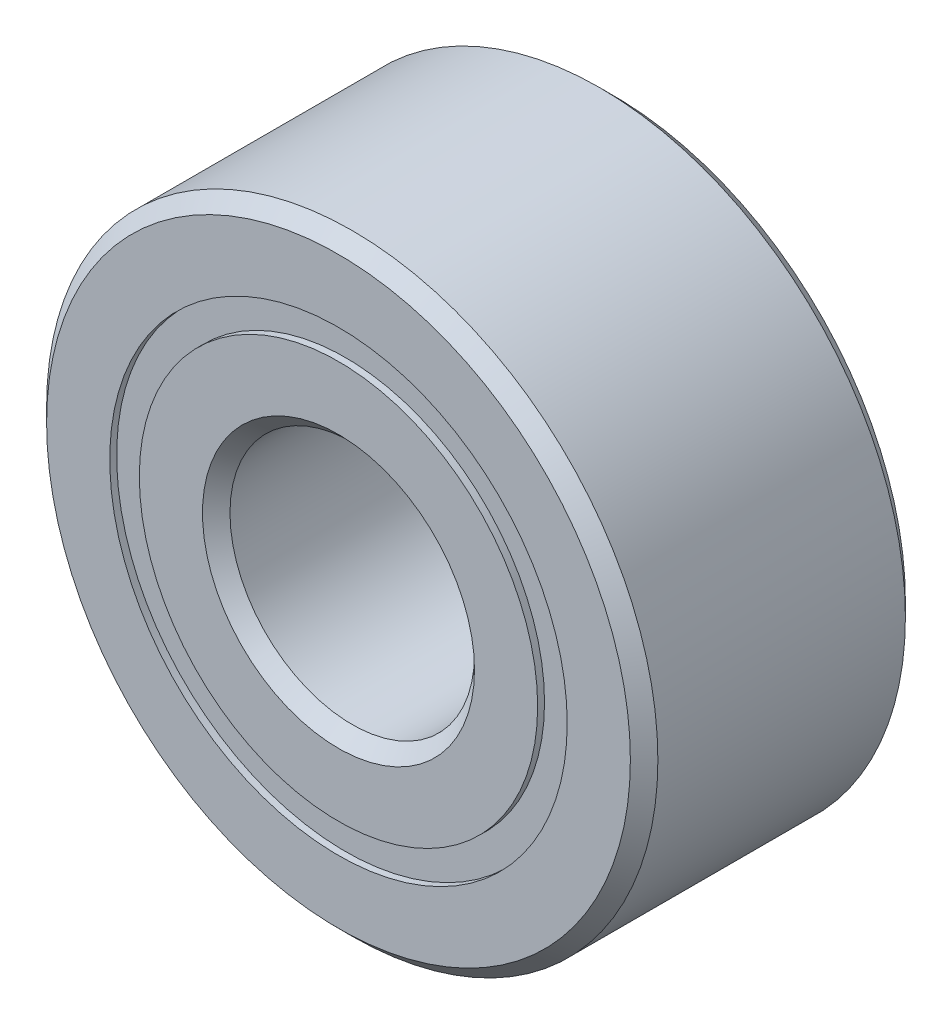
SolidWorks part; units mm, degrees
material "AISI 1020"
ref_plane "Front Plane" through (0, 0, 0) normal (0, 0, 1) x (1, 0, 0)
ref_plane "Top Plane" through (0, 0, 0) normal (0, 1, 0) x (1, 0, 0)
ref_plane "Right Plane" through (0, 0, 0) normal (1, 0, 0) x (0, 0, -1)
sketch "Sketch1" plane through (0, 0, 0) normal (1, 0, 0) x (0, 0, -1)
  line L0 (-1.7856, 0) -> (1.7856, 0) construction
  line L1 (0, 3.9688) -> (0, -3.9688) construction
  line L2 (1.6071, 3.9687) -> (-1.6071, 3.9687)
  line L3 (-1.6071, 3.9687) -> (-1.7856, 3.7902)
  line L4 (-1.7856, 3.7902) -> (-1.7856, 2.97)
  line L5 (-1.7856, 2.97) -> (-0.7936, 2.97)
  line L6 (1.7856, 2.97) -> (0.7936, 2.97)
  line L7 (1.7856, 3.7902) -> (1.7856, 2.97)
  line L8 (1.6071, 3.9687) -> (1.7856, 3.7902)
  line L9 (0, 3.9688) -> (0, 2.7781) construction
  line L10 (0, 2.7781) -> (0, 1.5875) construction
  arc A0 (-0.7936, 2.97) -> (0.7936, 2.97) centre (0, 2.7781) cw
  point P14 (0, 1.5875)
  dimension "D3" = 1.5872
  dimension "D1" = 45
  dimension "Width" = 3.5712
  dimension "OD" = 7.9375
  dimension "D2" = 0.1786
  dimension "Shaft Dia" = 3.175
  dimension "D4" = 0.1919
revolve "Revolve1" add sketch "Sketch1" angle 360 about L0
sketch "Sketch3" plane through (0, 0, 0) normal (1, 0, 0) x (0, 0, -1)
  line L0 (-0.7936, 2.5862) -> (-1.7856, 2.5862)
  line L1 (-1.7856, 3.7902) -> (-1.7856, 2.97) construction
  line L2 (-1.6071, 3.9687) -> (-1.7856, 3.7902) construction
  line L3 (-1.7856, 2.5862) -> (-1.7856, 1.7661)
  line L5 (-1.7856, 1.7661) -> (-1.6071, 1.5875)
  line L6 (-1.6071, 1.5875) -> (1.6071, 1.5875)
  line L7 (1.6071, 3.9687) -> (1.6071, -3.9687) construction
  line L8 (1.6071, 1.5875) -> (1.7856, 1.7661)
  line L9 (1.7856, -3.7902) -> (1.7856, 3.7902) construction
  line L10 (1.7856, 1.7661) -> (1.7856, 2.5862)
  line L11 (1.7856, 2.5862) -> (0.7936, 2.5862)
  line L12 (0, 3.9688) -> (0, -3.9688) construction
  line L13 (1.6071, 3.9687) -> (1.7856, 3.7902) construction
  arc A1 (0.7936, 2.5862) -> (-0.7936, 2.5862) centre (0, 2.7781) cw
  arc A2 (0.7936, 2.97) -> (-0.7936, 2.97) centre (0, 2.7781) ccw construction
revolve "Revolve3" add sketch "Sketch3" angle 360 about L0
sketch "Sketch4" plane through (0, 0, 0) normal (1, 0, 0) x (0, 0, -1)
  line L0 (-0.8165, 2.7781) -> (0.8165, 2.7781)
  arc A2 (-0.8165, 2.7781) -> (0.8165, 2.7781) centre (0, 2.7781) cw
  arc A3 (0.7936, 2.97) -> (-0.7936, 2.97) centre (0, 2.7781) ccw construction
revolve "Revolve4" add sketch "Sketch4" angle 360 about L0
ref_axis "Axis1" through (0, 0, -1.7856) along (0, 0, 1)
pattern_circular "CirPattern1" count 10 every 36 about axis through (0, 0, -1.7856) along (0, 0, 1) of bodies 104
sketch "Sketch5" plane through (0, 0, 0) normal (1, 0, 0) x (0, 0, -1)
  line L0 (-1.7856, 2.97) -> (-0.7936, 2.97) construction
  line L1 (-1.6963, 2.97) -> (-0.8165, 2.97)
  line L2 (-1.6963, 2.97) -> (-1.6963, 2.5862)
  line L3 (-1.6963, 2.5862) -> (-0.8165, 2.5862)
  line L4 (-0.8165, 2.97) -> (-0.8165, 2.5862)
  line L5 (-0.7936, 2.5862) -> (-1.7856, 2.5862) construction
  line L6 (1.7856, 2.97) -> (0.7936, 2.97) construction
  line L7 (1.6963, 2.97) -> (0.8165, 2.97)
  line L8 (1.6963, 2.97) -> (1.6963, 2.5862)
  line L9 (1.6963, 2.5862) -> (0.8165, 2.5862)
  line L10 (0.8165, 2.97) -> (0.8165, 2.5862)
  line L11 (1.7856, 2.5862) -> (0.7936, 2.5862) construction
  line L12 (-1.6071, 3.9687) -> (-1.7856, 3.7902) construction
  point P18 (-1.6963, 3.8795)
revolve "Revolve5" add sketch "Sketch5" angle 360 about L0
equation "\"D2@Sketch1\" = \"Width@Sketch1\"*.05"
equation "\"D3@Sketch1\" = \"Width@Sketch1\"/2.25"
equation "\"D4@Sketch1\" = (((\"OD@Sketch1\"-\"Width@Sketch1\")/2)/3.25)/3.5"
equation "\"D2@CirPattern1\" = 360/\"Balls@CirPattern1\""
